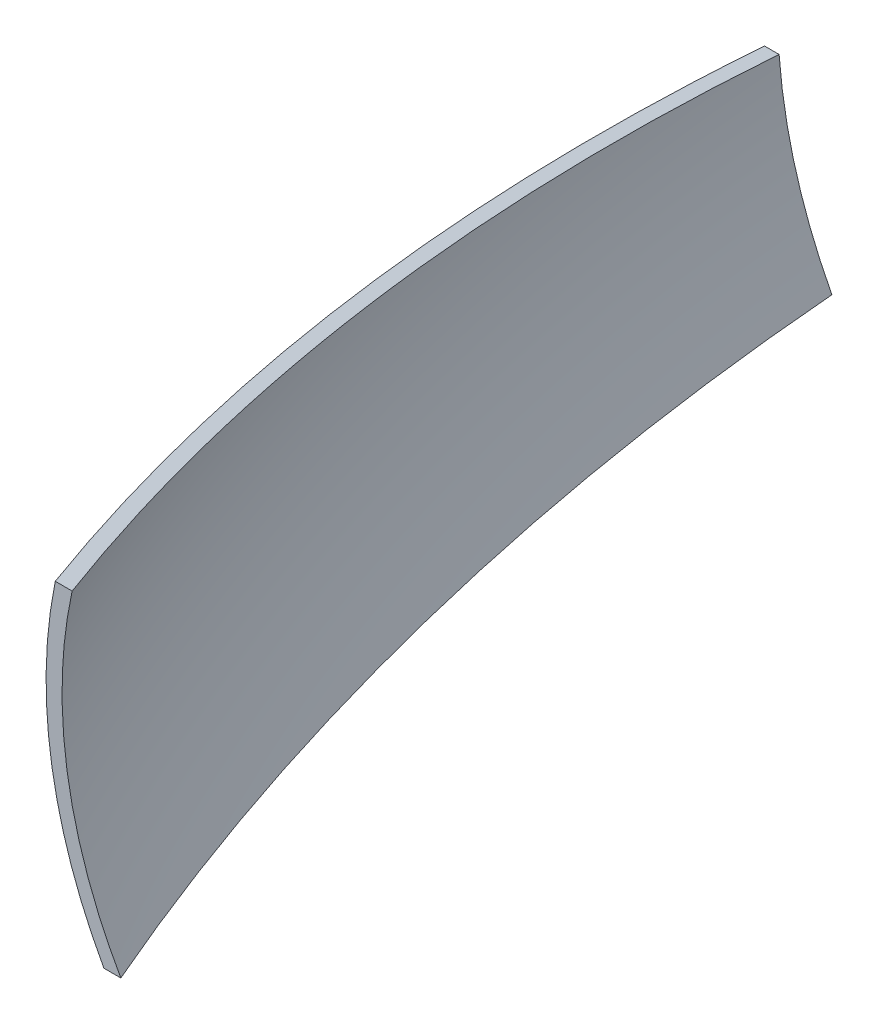
SolidWorks part; units mm, degrees
ref_plane "Front Plane" through (0, 0, 0) normal (0, 0, 1) x (1, 0, 0)
ref_plane "Top Plane" through (0, 0, 0) normal (0, 1, 0) x (1, 0, 0)
ref_plane "Right Plane" through (0, 0, 0) normal (1, 0, 0) x (0, 0, -1)
sketch "Sketch2" plane through (0, 0, 0) normal (0, 0, 1) x (1, 0, 0)
  line L0 (72.3704, 0) -> (82.3704, 0)
  line L1 (43.5787, 200) -> (53.5787, 200)
  arc A0 (72.3704, 0) -> (43.5787, 200) centre (349.5175, 141.9701) cw
  arc A1 (82.3704, 0) -> (53.5787, 200) centre (347.8898, 140.2962) cw
  dimension "D1" = 200
  dimension "D2" = 10
sketch "Sketch3" plane through (0, 0, 0) normal (0, 0, 1) x (1, 0, 0)
  line L0 (2000, -13.3717) -> (2000, 182.6602)
  line L1 (0, -403.9611) -> (0, 403.9611) construction
  dimension "D1" = 2000
revolve "Revolve1" add sketch "Sketch2" angle 88 about L0
sketch "Sketch5" plane through (0, 0, 0) normal (1, 0, 0) x (0, 0, -1)
  line L0 (-762.4592, 200) -> (-762.4592, 0)
  line L1 (-762.4592, 0) -> (-152.8592, 0)
  line L2 (-152.8592, 0) -> (-152.8592, 116.9512)
  line L3 (-152.8592, 116.9512) -> (-762.4592, 200)
  line L4 (0, 200) -> (-1945.2356, 200) construction
  line L5 (1078.3746, 0) -> (-1078.3746, 0) construction
  line L7 (-2824.2265, 1130.828) -> (2976.3022, 1130.828)
  line L8 (-2824.2265, 1130.828) -> (-2824.2265, -1305.0611)
  line L9 (-2824.2265, -1305.0611) -> (2976.3022, -1305.0611)
  line L10 (2976.3022, 1130.828) -> (2976.3022, -1305.0611)
  line L11 (-2824.2265, 1130.828) -> (2976.3022, -1305.0611) construction
  line L12 (-2824.2265, -1305.0611) -> (2976.3022, 1130.828) construction
  point P8 (76.0379, -87.1165)
  point P13 (-2824.2265, 1130.828)
  point P14 (2976.3022, -1305.0611)
  dimension "D1" = 609.6
extrude "Cut-Extrude2" cut sketch "Sketch5" against normal through all both and the other way through all
equation "\"shovelWidth\"= 2ft"
equation "\"D1@Sketch5\"=\"shovelWidth\""
